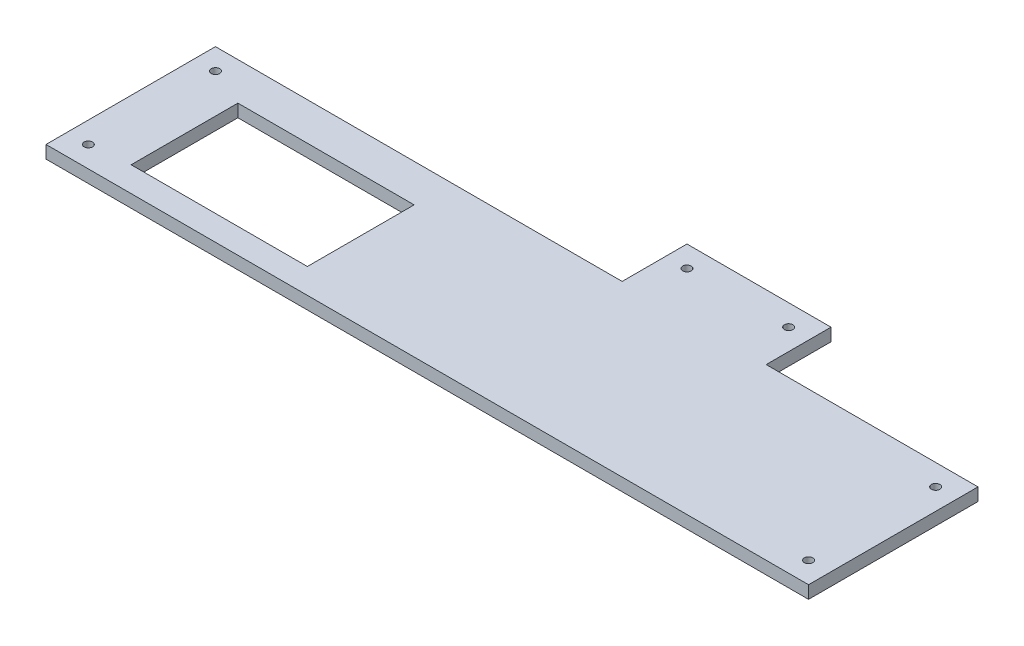
SolidWorks part; units mm, degrees
ref_plane "Front Plane" through (0, 0, 0) normal (0, 0, 1) x (1, 0, 0)
ref_plane "Top Plane" through (0, 0, 0) normal (0, 1, 0) x (1, 0, 0)
ref_plane "Right Plane" through (0, 0, 0) normal (1, 0, 0) x (0, 0, -1)
sketch "Sketch1" plane through (0, 0, 0) normal (0, 1, 0) x (1, 0, 0)
  line L0 (0, 0) -> (-450, 0) construction
  line L1 (0, 0) -> (0, 100) construction
  line L8 (450, 100) -> (-450, 100)
  line L9 (-450, 100) -> (-450, -100)
  line L10 (-450, -100) -> (450, -100)
  line L11 (450, -100) -> (450, 100)
  circle A4 centre (425, -75) radius 5
  circle A5 centre (425, 75) radius 5
  circle A6 centre (-425, -75) radius 5
  circle A7 centre (-425, 75) radius 5
  point P9 (0, 0)
  point P10 (0, 0)
  dimension "D4" = 25
  dimension "D1" = 900
  dimension "D2" = 200
  dimension "D3" = 25
extrude "Boss-Extrude1" add sketch "Sketch1" against normal blind 15
sketch "Sketch2" plane through (0, -15, 0) normal (0, -1, 0) x (1, 0, 0)
  line L1 (-379, 70.5) -> (-171, 70.5)
  line L2 (-379, 70.5) -> (-379, -55.5)
  line L3 (-379, -55.5) -> (-171, -55.5)
  line L4 (-171, 70.5) -> (-171, -55.5)
extrude "Shredder Opening" cut sketch "Sketch2" against normal through all
sketch "Sketch3" plane through (0, 0, 0) normal (0, 1, 0) x (1, 0, 0)
  line L0 (450, 100) -> (-450, 100) construction
  line L1 (200, 100) -> (30, 100)
  line L2 (200, 100) -> (200, 176.5)
  line L3 (200, 176.5) -> (30, 176.5)
  line L4 (30, 100) -> (30, 176.5)
  line L5 (180, -81.5) -> (180, 156.5) construction
  line L6 (50, 156.5) -> (180, 156.5) construction
  line L7 (50, -81.5) -> (50, 156.5) construction
  line L8 (115, 176.5) -> (115, 267.7218) construction
  circle A0 centre (175, 151.5) radius 5 construction
  circle A1 centre (175, 151.5) radius 5
  circle A2 centre (55, 151.5) radius 5
  dimension "D1" = 20
  dimension "D2" = 20
  dimension "D3" = 20
extrude "Legs add on" add sketch "Sketch3" against normal through all
